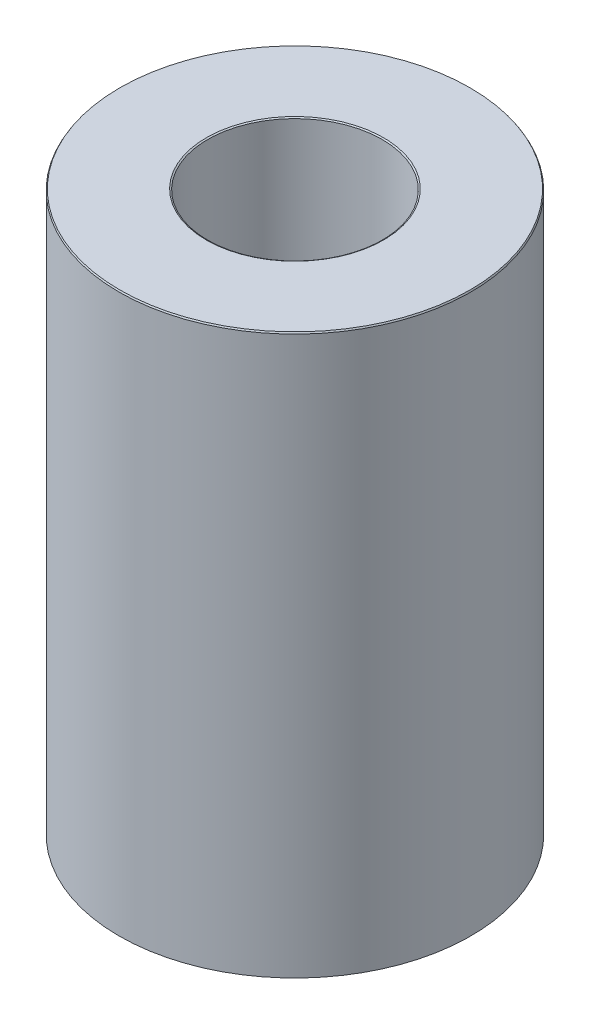
SolidWorks part; units mm, degrees
ref_plane "Front Plane" through (0, 0, 0) normal (0, 0, 1) x (1, 0, 0)
ref_plane "Top Plane" through (0, 0, 0) normal (0, 1, 0) x (1, 0, 0)
ref_plane "Right Plane" through (0, 0, 0) normal (1, 0, 0) x (0, 0, -1)
sketch "Sketch1" plane through (0, 0, 0) normal (0, 1, 0) x (1, 0, 0)
  circle A0 centre (0, 0) radius 57.5
  dimension "SLEEVE_OD" = 115
extrude "Boss-Extrude1" add sketch "Sketch1" along normal blind 182.9919
sketch "Sketch2" plane through (0, 0, 0) normal (0, 1, 0) x (1, 0, 0)
  circle A0 centre (0, 0) radius 28.5148
  dimension "BORE_D" = 57.0297
extrude "Cut-Extrude1" cut sketch "Sketch2" along normal through all
chamfer "Chamfer1" distance 0.4569 angle 30.326 4 edges at (0, 182.9919, 28.5148) (0, 0, 28.5148) (0, 0, 57.5) (0, 182.9919, 57.5) first distance on face at (0, 182.9919, 28.5148) first distance on face at (0, 0, 28.5148) first distance on face at (0, 182.9919, 57.5)
